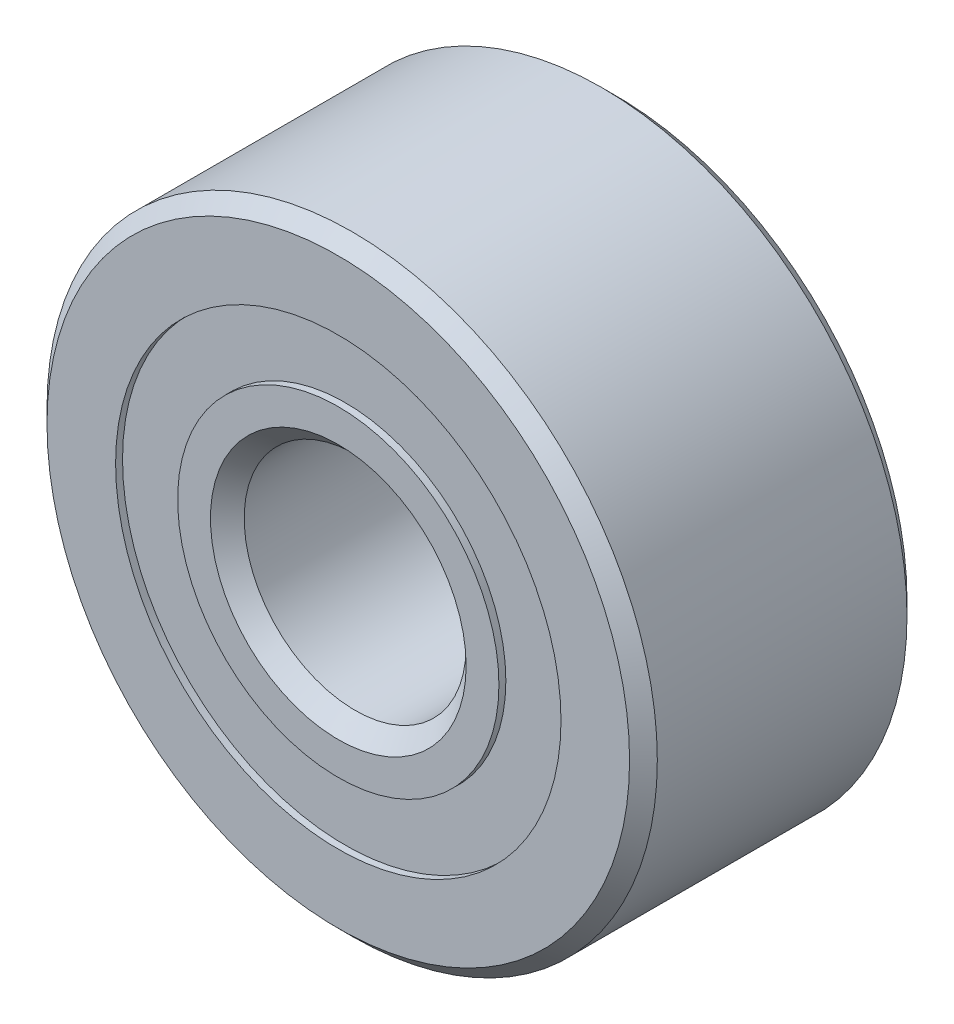
SolidWorks part; units mm, degrees
ref_plane "Front Plane" through (0, 0, 0) normal (0, 0, 1) x (1, 0, 0)
ref_plane "Top Plane" through (0, 0, 0) normal (0, 1, 0) x (1, 0, 0)
ref_plane "Right Plane" through (0, 0, 0) normal (1, 0, 0) x (0, 0, -1)
sketch "Sketch1" plane through (0, 0, 0) normal (1, 0, 0) x (0, 0, -1)
  line L0 (-3.9688, 0) -> (3.9688, 0) construction
  line L1 (0, 8.7312) -> (0, -8.7312) construction
  line L2 (3.5719, 8.7313) -> (-3.5719, 8.7312)
  line L3 (-3.5719, 8.7312) -> (-3.9688, 8.3344)
  line L4 (-3.9688, 8.3344) -> (-3.9688, 6.3718)
  line L5 (-3.9688, 6.3718) -> (-1.7639, 6.3718)
  line L6 (3.9688, 6.3718) -> (1.7639, 6.3718)
  line L7 (3.9688, 8.3344) -> (3.9688, 6.3718)
  line L8 (3.5719, 8.7313) -> (3.9688, 8.3344)
  line L9 (0, 8.7312) -> (0, 5.9531) construction
  line L10 (0, 5.9531) -> (0, 3.175) construction
  arc A0 (-1.7639, 6.3718) -> (1.7639, 6.3718) centre (0, 5.9531) cw
  point P14 (0, 3.175)
  dimension "Width" = 7.9375
  dimension "OD" = 17.4625
  dimension "D1" = 45
  dimension "D2" = 0.3969
  dimension "D3" = 3.5278
  dimension "D4" = 0.4187
revolve "Revolve1" add sketch "Sketch1" angle 360 about L0
sketch "Sketch2" plane through (0, 0, 0) normal (1, 0, 0) x (0, 0, -1)
  line L0 (-3.7703, 5.5344) -> (-1.7639, 5.5344)
  line L1 (-3.9688, 8.3344) -> (-3.9688, -8.3344) construction
  line L2 (-3.9688, 4.596) -> (-3.7703, 4.596) construction
  line L3 (-3.7703, 4.3976) -> (-3.0303, 3.6576)
  line L4 (-3.0303, 3.6576) -> (0, 3.6576)
  line L5 (0, 8.7312) -> (0, -8.7312) construction
  line L6 (0, 3.6576) -> (0, 4.1402)
  line L7 (0, 4.1402) -> (0, 3.175) construction
  line L8 (-3.9688, 5.5344) -> (-3.9688, 3.6576) construction
  line L9 (-3.9688, 3.6576) -> (-3.0303, 3.6576) construction
  line L10 (-3.7703, 5.5344) -> (-3.7703, 4.3976)
  line L11 (-3.7703, 5.5344) -> (-3.7703, 8.5328) construction
  line L12 (-3.5719, 8.7312) -> (-3.9688, 8.3344) construction
  arc A0 (-1.7639, 5.5344) -> (0, 4.1402) centre (0, 5.9531) ccw
  arc A1 (1.7639, 6.3718) -> (-1.7639, 6.3718) centre (0, 5.9531) ccw construction
  circle A2 centre (0, 5.9531) radius 1.8129 construction
  dimension "D1" = 45
revolve "Revolve2" [suppressed] add sketch "Sketch2" angle 360 about L0
sketch "Sketch3" plane through (0, 0, 0) normal (1, 0, 0) x (0, 0, -1)
  line L0 (-3.7703, 4.3976) -> (-3.0303, 3.6576)
  line L1 (-3.0303, 3.6576) -> (0, 3.6576)
  line L2 (0, 3.6576) -> (0, 4.1402)
  line L3 (-3.9688, 4.596) -> (-3.9688, 3.6576)
  line L4 (-3.9688, 5.5344) -> (-3.9688, 3.6576) construction
  line L5 (-3.9688, 3.6576) -> (-3.4861, 3.175)
  line L6 (-3.4861, 3.175) -> (3.5719, 3.175)
  line L7 (3.5719, 8.7313) -> (3.5719, -8.7313) construction
  line L8 (3.5719, 3.175) -> (3.9688, 3.5719)
  line L9 (3.9688, -8.3344) -> (3.9688, 8.3344) construction
  line L10 (3.9688, 3.5719) -> (3.9688, 5.5344)
  line L11 (3.9688, 5.5344) -> (1.7639, 5.5344)
  line L12 (-3.9688, 4.596) -> (-3.7703, 4.596)
  line L13 (3.5719, 8.7313) -> (3.9688, 8.3344) construction
  line L14 (-3.7703, 4.596) -> (-3.7703, 4.3976)
  circle A0 centre (0, 5.9531) radius 1.8129 construction
  arc A1 (1.7639, 5.5344) -> (0, 4.1402) centre (0, 5.9531) cw
revolve "Revolve3" add sketch "Sketch3" angle 360 about L0
sketch "Sketch4" plane through (0, 0, 0) normal (1, 0, 0) x (0, 0, -1)
  line L0 (-1.8129, 5.9531) -> (1.8129, 5.9531)
  circle A1 centre (0, 5.9531) radius 1.8129 construction
  arc A2 (-1.8129, 5.9531) -> (1.8129, 5.9531) centre (0, 5.9531) cw
  arc A3 (1.7639, 6.3718) -> (-1.7639, 6.3718) centre (0, 5.9531) ccw construction
revolve "Revolve4" add sketch "Sketch4" angle 360 about L0
ref_axis "Axis1" through (0, 0, -3.9688) along (0, 0, 1)
pattern_circular "CirPattern1" count 8 every 45 about axis through (0, 0, -3.9688) along (0, 0, 1) of bodies 104
sketch "Sketch5" plane through (0, 0, 0) normal (1, 0, 0) x (0, 0, -1)
  line L0 (-3.9688, 6.3718) -> (-1.7639, 6.3718) construction
  line L1 (-3.7703, 6.3718) -> (-1.8129, 6.3718)
  line L2 (-3.7703, 6.3718) -> (-3.7703, 4.596)
  line L3 (-3.7703, 4.596) -> (-1.8129, 4.596)
  line L4 (-1.8129, 6.3718) -> (-1.8129, 4.596)
  line L6 (-3.5719, 8.7312) -> (-3.9688, 8.3344) construction
  line L7 (0, 8.7312) -> (0, 3.175) construction
  line L8 (3.7703, 4.596) -> (1.8129, 4.596)
  line L9 (1.8129, 6.3718) -> (1.8129, 4.596)
  line L10 (3.7703, 6.3718) -> (1.8129, 6.3718)
  line L11 (3.7703, 6.3718) -> (3.7703, 4.596)
  circle A0 centre (0, 5.9531) radius 1.8129 construction
  point P10 (-3.7703, 8.5328)
revolve "Revolve5" add sketch "Sketch5" angle 360 about L0
equation "\"D2@Sketch1\" = \"Width@Sketch1\"*.05"
equation "\"D3@Sketch1\" = \"Width@Sketch1\"/2.25"
equation "\"D4@Sketch1\" = (((\"OD@Sketch1\"-\"Width@Sketch1\")/2)/3.25)/3.5"
equation "\"D2@CirPattern1\" = 360/\"Balls@CirPattern1\""
